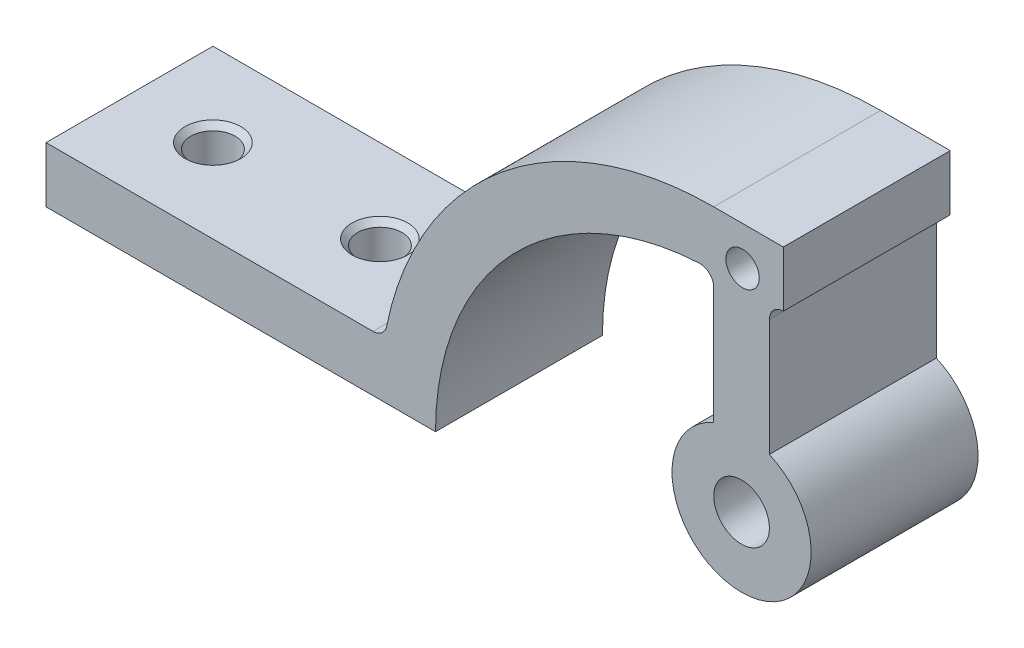
SolidWorks part; units mm, degrees
ref_plane "Front Plane" through (0, 0, 0) normal (0, 0, 1) x (1, 0, 0)
ref_plane "Top Plane" through (0, 0, 0) normal (0, 1, 0) x (1, 0, 0)
ref_plane "Right Plane" through (0, 0, 0) normal (1, 0, 0) x (0, 0, -1)
sketch "Sketch2" plane through (0, 0, 0) normal (0, 1, 0) x (1, 0, 0)
  line L0 (12.5, 7.5) -> (12.5, -7.5) construction
  line L1 (17.5, -7.5) -> (-17.5, -7.5)
  line L2 (17.5, -7.5) -> (17.5, 7.5)
  line L3 (17.5, 7.5) -> (-17.5, 7.5)
  line L4 (-17.5, -7.5) -> (-17.5, 7.5)
  line L5 (17.5, -7.5) -> (-17.5, 7.5) construction
  line L6 (17.5, 7.5) -> (-17.5, -7.5) construction
  circle A0 centre (-10, 0) radius 2
  circle A1 centre (5, 0) radius 2
  point P0 (0, 0)
  point P12 (0, 0)
  dimension "D5" = 4
  dimension "D6" = 4
  dimension "D1" = 15
  dimension "D2" = 35
  dimension "D3" = 15
  dimension "D4" = 10
  dimension "D7" = 5
extrude "Boss-Extrude1" add sketch "Sketch2" along normal blind 5
sketch "Sketch6" plane through (0, 0, 7.5) normal (0, 0, 1) x (1, 0, 0)
  line L0 (17.5, 0) -> (42.5, 0) construction
  line L1 (42.5, 0) -> (42.5, 25) construction
  line L2 (17.5, 0) -> (12.5, 0) construction
  line L4 (17.5, 0) -> (12.5, 0)
  line L5 (42.5, 30) -> (42.5, 33.8253) construction
  line L6 (42.5, 30) -> (47.5, 30)
  line L7 (42.5, 25) -> (42.5, 7.5)
  line L8 (42.5, 7.5) -> (47.5, 7.5)
  line L9 (47.5, 30) -> (47.5, 7.5)
  arc A0 (42.5, 30) -> (12.5, 0) centre (42.5, 0) ccw
  arc A1 (42.5, 25) -> (17.5, 0) centre (42.5, 0) ccw
  dimension "D1" = 60
  dimension "D2" = 50
  dimension "D3" = 5
  dimension "D4" = 22.5
extrude "Boss-Extrude6" add sketch "Sketch6" against normal blind 15
sketch "Sketch8" plane through (0, 0, 7.5) normal (0, 0, 1) x (1, 0, 0)
  line L0 (42.5, 7.5) -> (47.5, 7.5) construction
  circle A0 centre (45, 7.5) radius 6.25
  dimension "D1" = 12.5
extrude "Boss-Extrude7" add sketch "Sketch8" against normal blind 15
sketch "Sketch10" plane through (0, 0, 7.5) normal (0, 0, 1) x (1, 0, 0)
  circle A0 centre (45, 7.5) radius 2.5
  dimension "D1" = 5
extrude "Cut-Extrude1" cut sketch "Sketch10" against normal blind 15
chamfer "Chamfer1" distance 0.5 angle 45 2 edges at (5, 5, 2) (-10, 5, 2)
sketch "Sketch12" plane through (0, 0, 7.5) normal (0, 0, 1) x (1, 0, 0)
  line L1 (47.5, 30) -> (48.75, 30)
  line L2 (47.5, 30) -> (47.5, 25)
  line L3 (47.5, 25) -> (48.75, 25)
  line L4 (48.75, 30) -> (48.75, 25)
  dimension "D1" = 1.25
  dimension "D2" = 5
extrude "Boss-Extrude8" add sketch "Sketch12" against normal blind 15
fillet "Fillet2" radius 1.25 3 edges at (47.5, 25, 0) (42.5, 25, 0) (12.9196, 5, 0)
sketch "Sketch16" plane through (0, 0, 7.5) normal (0, 0, 1) x (1, 0, 0)
  circle A0 centre (45.0915, 26.5) radius 1.5
  dimension "D1" = 3
  dimension "D2" = 3.5
extrude "Cut-Extrude3" cut sketch "Sketch16" against normal blind 15
